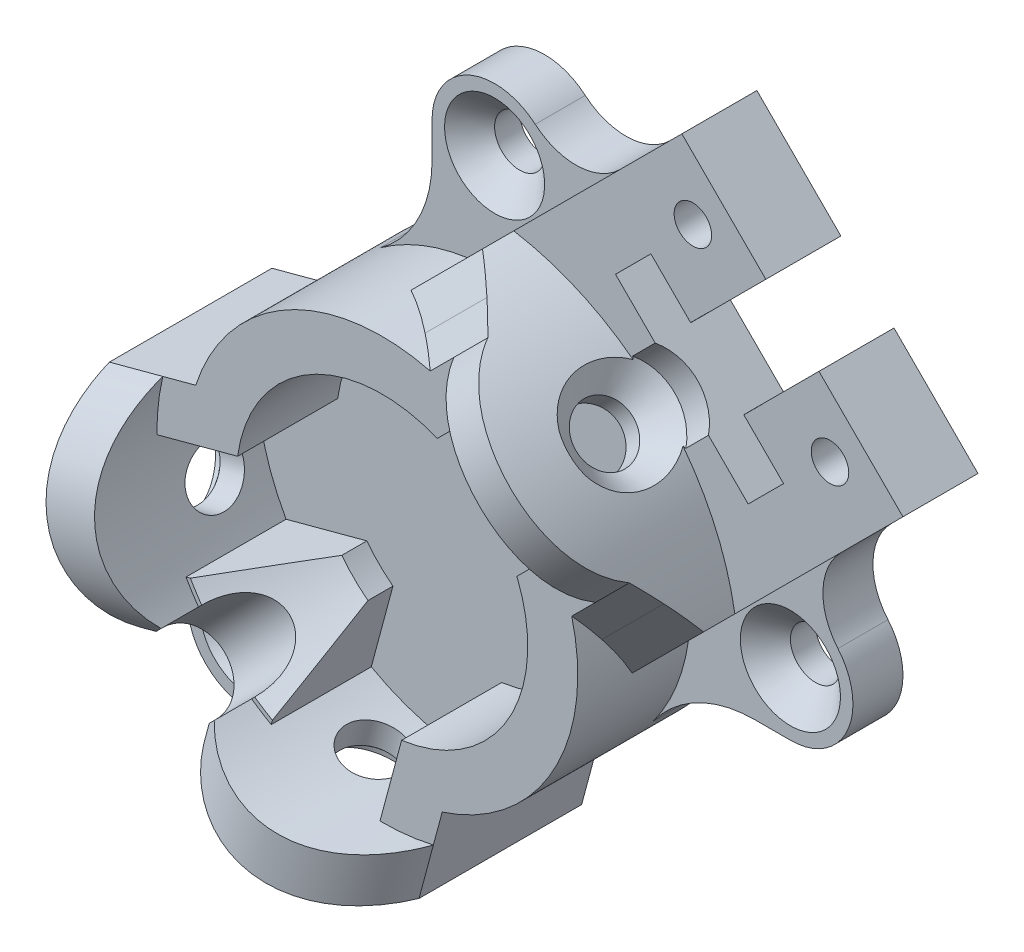
SolidWorks part; units mm, degrees
ref_plane "Top Plane" through (0, 0, 0) normal (0, 0, 1) x (1, 0, 0)
ref_plane "Right Plane" through (0, 0, 0) normal (0, 1, 0) x (1, 0, 0)
ref_plane "Front Plane" through (0, 0, 0) normal (1, 0, 0) x (0, 0, -1)
sketch "Sketch1" plane through (0, 0, 0) normal (0, 0, 1) x (1, 0, 0)
  line L0 (0, 0) -> (-12.3744, -12.3744) construction
  line L4 (-4.5293, -16.9037) -> (0, 0) construction
  line L5 (0, 0) -> (-16.9037, -4.5293) construction
  line L6 (-12.3744, -12.3744) -> (-17.5, -17.5) construction
  line L7 (17.5, -17.5) -> (-17.5, -17.5) construction
  line L8 (-6.5574, -9.0179) -> (-8.2731, -15.4209)
  line L9 (-0.5457, -17.4915) -> (1.17, -11.0884)
  line L10 (-11.0884, 1.17) -> (-17.4915, -0.5457)
  line L11 (-15.4209, -8.2731) -> (-9.0179, -6.5574)
  line L12 (17.5, -17.5) -> (17.5, 17.5)
  line L13 (17.5, 17.5) -> (-17.5, 17.5)
  line L14 (-17.5, -17.5) -> (-17.5, 17.5) construction
  line L15 (17.5, -17.5) -> (-17.5, 17.5) construction
  line L16 (-17.4915, -0.5457) -> (-17.5, -0.548)
  line L17 (-15.4209, -8.2731) -> (-17.5, -8.8302)
  line L18 (-8.2731, -15.4209) -> (-8.8302, -17.5)
  line L19 (-0.5457, -17.4915) -> (-0.548, -17.5)
  line L20 (-17.5, 17.5) -> (-17.5, -0.548)
  line L21 (-17.5, -8.8302) -> (-17.5, -17.5)
  line L22 (-17.5, -17.5) -> (-8.8302, -17.5)
  line L23 (-0.548, -17.5) -> (17.5, -17.5)
  line L24 (10.1879, 4.531) -> (14.8752, 9.2184)
  line L25 (0, 0) -> (12.3744, 12.3744) construction
  line L26 (4.531, 10.1879) -> (9.2184, 14.8752)
  circle A0 centre (0, 0) radius 11.15 construction
  circle A1 centre (0, 0) radius 17.5 construction
  arc A2 (14.8752, 9.2184) -> (9.2184, 14.8752) centre (0, 0) ccw
  arc A8 (-9.0179, -6.5574) -> (-6.5574, -9.0179) centre (0, 0) ccw
  arc A9 (-8.2731, -15.4209) -> (-0.5457, -17.4915) centre (0, 0) ccw construction
  arc A10 (1.17, -11.0884) -> (-11.0884, 1.17) centre (0, 0) ccw
  arc A11 (-17.4915, -0.5457) -> (-15.4209, -8.2731) centre (0, 0) ccw construction
  point P31 (12.3744, 12.3744)
  dimension "D1" = 22.3
  dimension "D2" = 35
  dimension "D3" = 35
  dimension "D4" = 8
  dimension "D5" = 8
  dimension "D6" = 8
  dimension "D7" = 30
  dimension "D8" = 30
sketch "Sketch2" plane through (0, 0, 0) normal (0, 0, 1) x (1, 0, 0)
  line L0 (-0.5457, -17.4915) -> (1.17, -11.0884) construction
  line L5 (-6.5574, -9.0179) -> (-8.2731, -15.4209) construction
  line L6 (-11.0884, 1.17) -> (-17.4915, -0.5457) construction
  line L7 (-15.4209, -8.2731) -> (-9.0179, -6.5574) construction
  line L8 (-0.5457, -17.4915) -> (1.17, -11.0884) construction
  line L9 (-6.5574, -9.0179) -> (-8.2731, -15.4209) construction
  line L10 (-11.0884, 1.17) -> (-17.4915, -0.5457) construction
  line L11 (-15.4209, -8.2731) -> (-9.0179, -6.5574) construction
  line L12 (0.2197, -18.4987) -> (1.9636, -11.9903)
  line L13 (-11.9903, 1.9636) -> (-18.4987, 0.2197)
  line L14 (-15.9105, -9.4396) -> (-9.4021, -7.6957)
  line L15 (-7.6957, -9.4021) -> (-9.4396, -15.9105)
  line L16 (11.3657, 4.2946) -> (16.1302, 9.0591)
  line L17 (12.3744, 12.3744) -> (13.0815, 13.0815) construction
  line L18 (9.0591, 16.1302) -> (4.2946, 11.3657)
  line L19 (0, 0) -> (12.3744, 12.3744) construction
  line L20 (10.1879, 4.531) -> (14.8752, 9.2184) construction
  line L21 (4.531, 10.1879) -> (9.2184, 14.8752) construction
  arc A0 (-9.0179, -6.5574) -> (-6.5574, -9.0179) centre (0, 0) ccw construction
  arc A1 (1.17, -11.0884) -> (-11.0884, 1.17) centre (0, 0) ccw construction
  arc A2 (-9.0179, -6.5574) -> (-6.5574, -9.0179) centre (0, 0) ccw construction
  arc A3 (1.17, -11.0884) -> (-11.0884, 1.17) centre (0, 0) ccw construction
  arc A4 (-17.4915, -0.5457) -> (-15.4209, -8.2731) centre (0, 0) ccw construction
  arc A5 (-8.2731, -15.4209) -> (-0.5457, -17.4915) centre (0, 0) ccw construction
  arc A6 (-9.4396, -15.9105) -> (0.2197, -18.4987) centre (0, 0) ccw
  arc A7 (1.9636, -11.9903) -> (11.3657, 4.2946) centre (0, 0) ccw
  arc A8 (-18.4987, 0.2197) -> (-15.9105, -9.4396) centre (0, 0) ccw
  arc A9 (-9.4021, -7.6957) -> (-7.6957, -9.4021) centre (0, 0) ccw
  arc A10 (16.1302, 9.0591) -> (9.0591, 16.1302) centre (0, 0) ccw
  arc A11 (4.2946, 11.3657) -> (-11.9903, 1.9636) centre (0, 0) ccw
  arc A12 (14.8752, 9.2184) -> (9.2184, 14.8752) centre (0, 0) ccw construction
  arc A14 (11.3657, 4.2946) -> (4.2946, 11.3657) centre (0, 0) ccw construction
  arc A15 (1.9636, -11.9903) -> (-11.9903, 1.9636) centre (0, 0) ccw construction
  point P34 (13.0815, 13.0815)
  dimension "D2" = 1
  dimension "D3" = 1
  dimension "D1" = 1
extrude "Boss-Extrude1" add sketch "Sketch2" against normal blind 5
sketch "Sketch4" plane through (0, 0, 0) normal (0, 0, 1) x (1, 0, 0)
  line L0 (-0.5457, -17.4915) -> (1.17, -11.0884) construction
  line L1 (-6.5574, -9.0179) -> (-8.2731, -15.4209) construction
  line L2 (-15.4209, -8.2731) -> (-9.0179, -6.5574) construction
  line L3 (-11.0884, 1.17) -> (-17.4915, -0.5457) construction
  line L4 (-0.5457, -17.4915) -> (1.17, -11.0884) construction
  line L5 (-6.5574, -9.0179) -> (-8.2731, -15.4209) construction
  line L6 (-15.4209, -8.2731) -> (-9.0179, -6.5574) construction
  line L7 (-11.0884, 1.17) -> (-17.4915, -0.5457) construction
  line L8 (-0.1641, -17.9993) -> (1.5654, -11.5443)
  line L9 (-11.5443, 1.5654) -> (-17.9993, -0.1641)
  line L10 (-15.6699, -8.8575) -> (-9.215, -7.1279)
  line L11 (-7.1279, -9.215) -> (-8.8575, -15.6699)
  line L21 (2.9585, -21.8002) -> (4.8094, -14.8927)
  line L22 (-14.8927, 4.8094) -> (-21.8002, 2.9585)
  line L23 (-17.4002, -13.4622) -> (-12.0208, -12.0208) construction
  line L24 (-12.0208, -12.0208) -> (-13.4622, -17.4002) construction
  line L26 (19.768, 8.4543) -> (13.0163, 1.7026)
  line L27 (1.7026, 13.0163) -> (8.4543, 19.768)
  line L28 (19.768, 8.4543) -> (15.168, 3.8543)
  line L29 (3.8543, 15.168) -> (8.4543, 19.768)
  line L30 (15.168, 3.8543) -> (11.6453, 0.3316) construction
  line L31 (0.3316, 11.6453) -> (3.8543, 15.168) construction
  line L32 (9.1418, 15.5057) -> (4.1775, 10.5414)
  line L33 (10.5414, 4.1775) -> (15.5057, 9.1418)
  line L34 (9.1418, 15.5057) -> (4.4165, 10.7804)
  line L35 (10.7804, 4.4165) -> (15.5057, 9.1418)
  arc A0 (-9.0179, -6.5574) -> (-6.5574, -9.0179) centre (0, 0) ccw construction
  arc A1 (1.17, -11.0884) -> (-11.0884, 1.17) centre (0, 0) ccw construction
  arc A2 (-9.0179, -6.5574) -> (-6.5574, -9.0179) centre (0, 0) ccw construction
  arc A3 (1.17, -11.0884) -> (-11.0884, 1.17) centre (0, 0) ccw construction
  arc A4 (-15.4209, -8.2731) -> (-17.4915, -0.5457) centre (0, 0) cw construction
  arc A5 (-8.2731, -15.4209) -> (-0.5457, -17.4915) centre (0, 0) ccw construction
  arc A6 (-8.8575, -15.6699) -> (-0.1641, -17.9993) centre (0, 0) ccw
  arc A7 (1.5654, -11.5443) -> (11.6453, 0.3316) centre (0, 0) ccw
  arc A8 (-15.6699, -8.8575) -> (-17.9993, -0.1641) centre (0, 0) cw
  arc A9 (-9.215, -7.1279) -> (-7.1279, -9.215) centre (0, 0) ccw
  arc A10 (-13.4622, -17.4002) -> (2.9585, -21.8002) centre (0, 0) ccw
  arc A11 (4.8094, -14.8927) -> (15.168, 3.8543) centre (0, 0) ccw
  arc A12 (-17.4002, -13.4622) -> (-21.8002, 2.9585) centre (0, 0) cw
  arc A13 (-12.0208, -12.0208) -> (-12.0208, -12.0208) centre (-12.0208, -12.0208) cw
  arc A14 (-17.4002, -13.4622) -> (-13.4622, -17.4002) centre (0, 0) ccw
  arc A17 (3.8543, 15.168) -> (-14.8927, 4.8094) centre (0, 0) ccw
  arc A18 (19.768, 8.4543) -> (8.4543, 19.768) centre (0, 0) ccw
  arc A19 (19.768, 8.4543) -> (8.4543, 19.768) centre (0, 0) ccw
  arc A20 (0.3316, 11.6453) -> (-11.5443, 1.5654) centre (0, 0) ccw
  arc A21 (15.168, 3.8543) -> (3.8543, 15.168) centre (0, 0) ccw construction
  arc A22 (4.8094, -14.8927) -> (-14.8927, 4.8094) centre (0, 0) ccw construction
  arc A24 (10.7804, 4.4165) -> (4.4165, 10.7804) centre (0, 0) ccw construction
  arc A25 (1.5654, -11.5443) -> (-11.5443, 1.5654) centre (0, 0) ccw construction
  arc A26 (11.6453, 0.3316) -> (10.7804, 4.4165) centre (0, 0) ccw
  arc A27 (15.5057, 9.1418) -> (9.1418, 15.5057) centre (0, 0) ccw
  arc A28 (15.5057, 9.1418) -> (9.1418, 15.5057) centre (0, 0) ccw
  arc A29 (4.4165, 10.7804) -> (0.3316, 11.6453) centre (0, 0) ccw
  point P30 (15.3806, 8.9996)
  arc M36 (-9.4396, -15.9105) -> (0.2197, -18.4987) centre (0, 0) ccw
  line M37 (0.2197, -18.4987) -> (1.9636, -11.9903)
  arc M38 (1.9636, -11.9903) -> (11.3657, 4.2946) centre (0, 0) ccw
  line M39 (-11.9903, 1.9636) -> (-18.4987, 0.2197)
  arc M40 (-18.4987, 0.2197) -> (-15.9105, -9.4396) centre (0, 0) ccw
  line M41 (-15.9105, -9.4396) -> (-9.4021, -7.6957)
  arc M42 (-9.4021, -7.6957) -> (-7.6957, -9.4021) centre (0, 0) ccw
  line M43 (-7.6957, -9.4021) -> (-9.4396, -15.9105)
  dimension "D2" = 4
  dimension "D1" = 0.5
  dimension "D3" = 4
  dimension "D4" = 0.5
extrude "Boss-Extrude2" add sketch "Sketch4" along normal blind 8 and the other way up to surface (5 mm away) contours A12 A14 A10 L21 A11 L22 M36 M43 M42 M41 M40 M39 M38 M37 | A9 L10 A8 L9 A7 L8 A6 L11 M43 M36 M37 M38 M39 M40 M41 M42 region at (-5.5411, -20.6798, 0) other way up to face at (-2.3894, -2.3894, -5)
sketch "Sketch6" plane through (0, 0, -5) normal (0, 0, -1) x (-1, 0, 0)
  line L0 (-14.8298, -5) -> (-23.65, -5)
  line L1 (-23.65, 5) -> (-14.8298, 5)
  line L2 (0, 0) -> (0, 23.65) construction
  line L3 (-5, 14.8298) -> (-5, 23.65)
  line L4 (5, 23.65) -> (5, 14.8298)
  line L5 (0, 23.65) -> (-23.65, 0) construction
  line L6 (-23.65, 0) -> (0, 0) construction
  line L7 (0, 0) -> (19.5515, -19.5515) construction
  line L8 (6.9507, -14.0218) -> (16.016, -23.087)
  line L9 (23.087, -16.016) -> (14.0218, -6.9507)
  line L10 (0, 0) -> (-11.825, 11.825) construction
  circle A0 centre (0, 23.65) radius 2
  circle A1 centre (-23.65, 0) radius 2
  arc A2 (-15.168, 3.8543) -> (-4.8094, -14.8927) centre (0, 0) ccw construction
  arc A3 (-23.65, -5) -> (-23.65, 5) centre (-23.65, 0) cw
  arc A4 (-5, 23.65) -> (5, 23.65) centre (0, 23.65) cw
  arc A5 (-14.8298, -5) -> (6.9507, -14.0218) centre (0, 0) ccw
  arc A6 (-14.8298, 5) -> (-14.8298, -5) centre (0, 0) ccw construction
  arc A7 (-5, 14.8298) -> (-14.8298, 5) centre (0, 0) ccw
  arc A8 (5, 14.8298) -> (-5, 14.8298) centre (0, 0) ccw construction
  circle A9 centre (19.5515, -19.5515) radius 2
  arc A10 (16.016, -23.087) -> (23.087, -16.016) centre (19.5515, -19.5515) ccw
  arc A11 (14.0218, -6.9507) -> (5, 14.8298) centre (0, 0) ccw
  arc A12 (11.0662, -11.0662) -> (14.0218, -6.9507) centre (0, 0) ccw construction
  arc A13 (6.9507, -14.0218) -> (11.0662, -11.0662) centre (0, 0) ccw construction
  point P18 (0, 15.65)
  dimension "D1" = 3
  dimension "D2" = 4
  dimension "D3" = 8
  dimension "D4" = 12
extrude "Boss-Extrude3" add sketch "Sketch6" against normal blind 4
chamfer "Chamfer2" distance 6 angle 45 1 edges at (-8.2378, -8.2378, 8)
sketch "Sketch7" plane through (0, 0, 8) normal (0, 0, 1) x (1, 0, 0)
  line L0 (-19.5515, -19.5515) -> (0, 0) construction
  line L2 (-19.5515, -19.5515) -> (-17.4302, -21.6728)
  line L3 (-19.5515, -19.5515) -> (0, 0)
  line L4 (0, 0) -> (2.1213, -2.1213)
  line L5 (-17.4302, -21.6728) -> (2.1213, -2.1213)
  circle A0 centre (-19.5515, -19.5515) radius 2 construction
  dimension "D1" = 3
revolve "Cut-Revolve1" cut sketch "Sketch7" angle 360 about L0
ref_plane "Plane2" through (0, 0, 0) normal (0.2588, -0.9659, 0) x (-0.9659, -0.2588, 0)
sketch "Sketch9" plane through (0, 0, 0) normal (0.2588, -0.9659, 0) x (-0.9659, -0.2588, 0)
  line L0 (18, 0) -> (18, -8) construction
  line L1 (25, -4) -> (0, -4)
  line L2 (25, -4) -> (25, -1.7)
  line L3 (25, -1.7) -> (0, -1.7)
  line L4 (0, -4) -> (0, -1.7)
  line L5 (17.4284, -8) -> (18, -8) construction
  line L9 (0, -1.7) -> (0, 0) construction
  point P13 (18, -4)
  dimension "D1" = 2.3
  dimension "D2" = 25
revolve "Cut-Revolve2" cut sketch "Sketch9" angle 360 about L1
ref_plane "Plane3" through (0, 0, 0) normal (0.7071, -0.7071, 0) x (0, 0, -1)
mirror "Mirror1" about plane through (0, 0, 0) normal (0.7071, -0.7071, 0) of "Cut-Revolve2"
sketch "Sketch10" plane through (0, 0, 8) normal (0, 0, 1) x (1, 0, 0)
  line L0 (15.4974, -2.1803) -> (34.6482, 16.9706)
  line L1 (34.6482, 16.9706) -> (16.9706, 34.6482)
  line L2 (16.9706, 34.6482) -> (-2.1803, 15.4974)
  line L3 (13.7809, 7.4169) -> (15.5057, 9.1418)
  line L4 (0, 0) -> (15.2028, 15.2028) construction
  line L5 (15.2028, 15.2028) -> (25.8094, 25.8094) construction
  line L6 (10.7804, 4.4165) -> (15.5057, 9.1418) construction
  line L8 (7.4169, 13.7809) -> (9.1418, 15.5057)
  line L9 (9.1418, 15.5057) -> (4.4165, 10.7804) construction
  arc A2 (-2.1803, 15.4974) -> (7.4169, 13.7809) centre (0, 0) cw
  arc A3 (19.768, 8.4543) -> (8.4543, 19.768) centre (0, 0) ccw construction
  arc A4 (4.8094, -14.8927) -> (15.168, 3.8543) centre (0, 0) ccw construction
  arc A5 (9.1418, 15.5057) -> (15.5057, 9.1418) centre (0, 0) cw
  arc A6 (13.7809, 7.4169) -> (15.4974, -2.1803) centre (0, 0) cw
  arc A7 (11.0662, 11.0662) -> (13.7809, 7.4169) centre (0, 0) cw construction
  arc A8 (7.4169, 13.7809) -> (11.0662, 11.0662) centre (0, 0) cw construction
  arc A9 (15.5057, 9.1418) -> (9.1418, 15.5057) centre (0, 0) ccw construction
  dimension "D1" = 15
  dimension "D2" = 25
extrude "Boss-Extrude4" add sketch "Sketch10" against normal up to surface (13 mm away) from offset 2 up to face at (0.5187, 0.5187, -5) offset against normal yes
sketch "Sketch11" plane through (25.8094, 25.8094, 0) normal (0.7071, 0.7071, 0) x (0, 0, -1)
  line L9 (5, -3.0025) -> (5, 3.0025)
  line L10 (5, 12.5) -> (5, -12.5) construction
  line L11 (5, -3.0025) -> (-1, -3.0025)
  line L12 (-1, -3.0025) -> (-1, -12.5)
  line L13 (5, -12.5) -> (-6, -12.5) construction
  line L14 (-1, -12.5) -> (-6, -12.5)
  line L15 (-6, -12.5) -> (-6, 12.5)
  line L16 (-6, 12.5) -> (-1, 12.5)
  line L17 (5, 12.5) -> (-6, 12.5) construction
  line L18 (-1, 12.5) -> (-1, 3.0025)
  line L19 (-1, 3.0025) -> (5, 3.0025)
  point P5 (5, 0)
  point P6 (5, 0)
  dimension "D1" = 6.005
  dimension "D2" = 6
extrude "Cut-Extrude1" cut sketch "Sketch11" against normal up to surface (15.2107 mm away) up to face at (14.657, 14.657, 7)
fillet "Fillet2" radius 5 2 edges at (5, 22.6777, -3) (22.6777, 5, -3)
fillet "Fillet3" radius 10 2 edges at (14.8298, -5, -3) (-5, 14.8298, -3)
chamfer "Chamfer4" distance 2 angle 45 3 edges at (21.65, 0, -1) (-2, 23.65, -1) (-21.5515, -19.5515, -1)
sketch "Sketch12" plane through (0, 0, 1) normal (0, 0, 1) x (1, 0, 0)
  line L0 (22.2739, 11.6673) -> (11.6673, 22.2739)
  line L1 (11.6673, 22.2739) -> (14.4957, 25.1023)
  line L2 (14.4957, 25.1023) -> (25.1023, 14.4957)
  line L3 (25.1023, 14.4957) -> (22.2739, 11.6673)
  line L4 (0, 0) -> (16.9706, 16.9706) construction
  line L5 (23.6863, 27.9325) -> (16.9706, 34.6482) construction
  line L6 (17.8536, 28.8155) -> (28.8155, 17.8536) construction
  line L7 (19.799, 19.799) -> (23.3345, 23.3345) construction
  line L8 (34.6482, 16.9706) -> (27.9325, 23.6863) construction
  line L9 (17.8536, 28.8155) -> (20.3284, 31.2904) construction
  circle A0 centre (17.8536, 28.8155) radius 1.5
  circle A1 centre (28.8155, 17.8536) radius 1.5
  point P12 (16.8862, 6.3537)
  point P13 (17.3014, 18.2373)
  point P14 (0, 0)
  point P15 (25.5798, 16.2535)
  point P20 (20.8263, 30.7925)
  point P23 (22.6419, 12.0353)
  dimension "D3" = 3
  dimension "D4" = 3.5
  dimension "D1" = 4
  dimension "D2" = 15
  dimension "D5" = 5
extrude "Cut-Extrude2" cut sketch "Sketch12" against normal through all
sketch "Sketch13" plane through (0, 0, 1) normal (0, 0, 1) x (1, 0, 0)
  line L0 (19.0936, 14.8475) -> (14.8475, 19.0936)
  line L4 (14.8475, 19.0936) -> (12.9307, 17.1769)
  line L5 (12.9307, 17.1769) -> (17.1769, 12.9307)
  line L6 (17.1769, 12.9307) -> (19.0936, 14.8475)
extrude "Boss-Extrude5" add sketch "Sketch13" against normal up to surface (6 mm away) up to face at (19.3536, 28.8155, -5)
sketch "Sketch16" plane through (0, 0, 8) normal (0, 0, 1) x (1, 0, 0)
  line L0 (-14.8927, 4.8094) -> (-21.8002, 2.9585) construction
  line L1 (2.9585, -21.8002) -> (4.8094, -14.8927) construction
  line L2 (3.8543, 15.168) -> (8.4543, 19.768) construction
  line L4 (-13.2897, -17.5324) -> (-10.1775, -14.4202) construction
  line L5 (-14.4202, -10.1775) -> (-17.5324, -13.2897) construction
  line L6 (19.768, 8.4543) -> (15.168, 3.8543) construction
  line L7 (-17.5324, -13.2897) -> (-14.6712, -10.4286)
  line L8 (2.9585, -21.8002) -> (4.1038, -17.526)
  line L9 (-13.2897, -17.5324) -> (-10.4286, -14.6712)
  line L10 (17.0586, 5.7449) -> (19.768, 8.4543)
  line L11 (-21.8002, 2.9585) -> (-17.526, 4.1038)
  line L12 (5.7449, 17.0586) -> (8.4543, 19.768)
  arc A0 (19.768, 8.4543) -> (8.4543, 19.768) centre (0, 0) ccw construction
  arc A1 (-13.2897, -17.5324) -> (2.9585, -21.8002) centre (0, 0) ccw construction
  arc A2 (-21.8002, 2.9585) -> (-17.5324, -13.2897) centre (0, 0) ccw construction
  arc A3 (19.768, 8.4543) -> (8.4543, 19.768) centre (0, 0) ccw
  arc A4 (-13.2897, -17.5324) -> (2.9585, -21.8002) centre (0, 0) ccw
  arc A5 (-21.8002, 2.9585) -> (-17.5324, -13.2897) centre (0, 0) ccw
  arc A6 (-17.526, 4.1038) -> (-14.6712, -10.4286) centre (0, 0) ccw
  arc A7 (-10.4286, -14.6712) -> (4.1038, -17.526) centre (0, 0) ccw
  arc A8 (5.7449, 17.0586) -> (17.0586, 5.7449) centre (0, 0) cw
  arc A9 (-8.8575, -15.6699) -> (-0.1641, -17.9993) centre (0, 0) ccw construction
  arc A10 (-17.9993, -0.1641) -> (-15.6699, -8.8575) centre (0, 0) ccw construction
  arc A11 (15.5057, 9.1418) -> (9.1418, 15.5057) centre (0, 0) ccw construction
extrude "Boss-Extrude9" add sketch "Sketch16" along normal blind 10
sketch "Sketch14" plane through (0, 0, 0) normal (0.7071, -0.7071, 0) x (0, 0, -1)
  line L0 (-4, -16.6107) -> (-4, 0) construction
  line L1 (-6.3, 0) -> (-4, 0)
  line L2 (-6.3, 0) -> (-6.3, 19.5)
  line L3 (-6.3, 30) -> (-4, 30)
  line L4 (-4, 0) -> (-4, 30)
  line L5 (-6.3, -15.5885) -> (-6.3, 0) construction
  line L9 (-6.3, 19.5) -> (-8.25, 21.45)
  line L10 (-8.25, 21.45) -> (-8.25, 30)
  line L11 (-8.25, 30) -> (-6.3, 30)
  line L12 (-6.3, 19.5) -> (-6.3, 30) construction
  spline S0 degree 3 poles (-4.3042, -16.6107) (-3.8479, -16.6107) (-3.6983, -16.6049) (-3.4042, -16.582) (-3.258, -16.5647) (-2.9796, -16.5188) (-2.8475, -16.4905) (-2.5976, -16.4225) (-2.4794, -16.3825) (-2.1616, -16.2485) (-1.9903, -16.137) (-1.7607, -15.8838) (-1.7002, -15.7392) (-1.6999, -15.514) (-1.7149, -15.4361) (-1.7736, -15.2822) (-1.8171, -15.2058) (-1.9324, -15.0546) (-2.0043, -14.9803) (-2.1707, -14.8404) (-2.2658, -14.774) (-2.4803, -14.6498) (-2.5963, -14.594) (-2.8452, -14.4953) (-2.9797, -14.452) (-3.2581, -14.3824) (-3.4014, -14.3559) (-3.6964, -14.32) (-3.849, -14.3107) (-4.2995, -14.3106) (-4.6024, -14.3477) (-5.0177, -14.4513) (-5.1516, -14.4941) (-5.4029, -14.5935) (-5.5187, -14.6493) (-5.7309, -14.7719) (-5.8281, -14.8394) (-5.9951, -14.9796) (-6.0658, -15.0526) (-6.1816, -15.2037) (-6.226, -15.2815) (-6.2848, -15.4349) (-6.2999, -15.5114) (-6.3001, -15.6635) (-6.2853, -15.7366) (-6.2271, -15.8774) (-6.1829, -15.9458) (-6.0677, -16.0732) (-5.9971, -16.1323) (-5.8304, -16.242) (-5.7335, -16.2926) (-5.4159, -16.4267) (-5.1596, -16.4958) (-4.6065, -16.5871) (-4.3042, -16.6107) (-3.8479, -16.6107) (-3.6983, -16.6049) knots -0.0625 -0.0625 0 0 0.03125 0.03125 0.0625 0.0625 0.09375 0.09375 0.125 0.125 0.1875 0.1875 0.25 0.25 0.28125 0.28125 0.3125 0.3125 0.34375 0.34375 0.375 0.375 0.40625 0.40625 0.4375 0.4375 0.46875 0.46875 0.5 0.5 0.5625 0.5625 0.59375 0.59375 0.625 0.625 0.65625 0.65625 0.6875 0.6875 0.71875 0.71875 0.75 0.75 0.78125 0.78125 0.8125 0.8125 0.84375 0.84375 0.875 0.875 0.9375 0.9375 1 1 1.03125 1.03125 1.0625 only from (-4, -16.6107) to (-4, -16.6107) construction
  spline S1 degree 3 poles (-4.3042, -16.6107) (-3.8479, -16.6107) (-3.6983, -16.6049) (-3.4042, -16.582) (-3.258, -16.5647) (-2.9796, -16.5188) (-2.8475, -16.4905) (-2.5976, -16.4225) (-2.4794, -16.3825) (-2.1616, -16.2485) (-1.9903, -16.137) (-1.7607, -15.8838) (-1.7002, -15.7392) (-1.6999, -15.514) (-1.7149, -15.4361) (-1.7736, -15.2822) (-1.8171, -15.2058) (-1.9324, -15.0546) (-2.0043, -14.9803) (-2.1707, -14.8404) (-2.2658, -14.774) (-2.4803, -14.6498) (-2.5963, -14.594) (-2.8452, -14.4953) (-2.9797, -14.452) (-3.2581, -14.3824) (-3.4014, -14.3559) (-3.6964, -14.32) (-3.849, -14.3107) (-4.2995, -14.3106) (-4.6024, -14.3477) (-5.0177, -14.4513) (-5.1516, -14.4941) (-5.4029, -14.5935) (-5.5187, -14.6493) (-5.7309, -14.7719) (-5.8281, -14.8394) (-5.9951, -14.9796) (-6.0658, -15.0526) (-6.1816, -15.2037) (-6.226, -15.2815) (-6.2848, -15.4349) (-6.2999, -15.5114) (-6.3001, -15.6635) (-6.2853, -15.7366) (-6.2271, -15.8774) (-6.1829, -15.9458) (-6.0677, -16.0732) (-5.9971, -16.1323) (-5.8304, -16.242) (-5.7335, -16.2926) (-5.4159, -16.4267) (-5.1596, -16.4958) (-4.6065, -16.5871) (-4.3042, -16.6107) (-3.8479, -16.6107) (-3.6983, -16.6049) knots -0.0625 -0.0625 0 0 0.03125 0.03125 0.0625 0.0625 0.09375 0.09375 0.125 0.125 0.1875 0.1875 0.25 0.25 0.28125 0.28125 0.3125 0.3125 0.34375 0.34375 0.375 0.375 0.40625 0.40625 0.4375 0.4375 0.46875 0.46875 0.5 0.5 0.5625 0.5625 0.59375 0.59375 0.625 0.625 0.65625 0.65625 0.6875 0.6875 0.71875 0.71875 0.75 0.75 0.78125 0.78125 0.8125 0.8125 0.84375 0.84375 0.875 0.875 0.9375 0.9375 1 1 1.03125 1.03125 1.0625 only from (-4, -16.6107) to (-4, -16.6107) construction
  dimension "D1" = 30
  dimension "D2" = 45
  dimension "D3" = 2
  dimension "D4" = 4.25
revolve "Cut-Revolve5" cut sketch "Sketch14" angle 360 about L4
sketch "Sketch17" plane through (25.8094, 25.8094, 0) normal (0.7071, 0.7071, 0) x (0, 0, -1)
  line L0 (-8, -8) -> (-8, -10)
  line L1 (-8, -10) -> (-18, -10)
  line L2 (-18, -10) -> (-18, 10)
  line L3 (-18, 10) -> (-8, 10)
  line L4 (-8, 10) -> (-8, 8)
  arc A0 (-8, -8) -> (-8, 8) centre (-4, 0) cw
  circle A2 centre (-4, 0) radius 2.3 construction
  dimension "D1" = 20
  dimension "D2" = 10
extrude "Cut-Extrude3" cut sketch "Sketch17" against normal blind 30
chamfer "Chamfer5" distance 2 angle 45 2 edges at (6.1543, 17.468, 6) (17.468, 6.1543, 6)
ref_axis "Axis1" through (0, 0, -5) along (0, 0, 1)
ref_plane "Plane4" through (-21.2504, -5.694, 0) normal (-0.9659, -0.2588, 0) x (0, 0, 1)
sketch "Sketch18" plane through (-21.2504, -5.694, 0) normal (-0.9659, -0.2588, 0) x (0, 0, 1)
  line L0 (8, -6.0985) -> (8, -6.276) construction
  line L1 (8, 8.5) -> (8, 10)
  line L2 (8, 10) -> (18, 10)
  line L3 (18, 10) -> (18, -10)
  line L4 (18, -10) -> (8, -10)
  line L5 (8, -10) -> (8, -8.5)
  arc A0 (8, 8.5) -> (8, -8.5) centre (4, 0) cw
  circle A2 centre (4, 0) radius 2.3 construction
  dimension "D1" = 20
  dimension "D2" = 10
extrude "Cut-Extrude4" cut sketch "Sketch18" against normal blind 30
sketch "Sketch19" plane through (0, 0, 0) normal (0.2588, -0.9659, 0) x (-0.9659, -0.2588, 0)
  line L0 (0, -4) -> (26.5, -4)
  line L1 (26.5, -4) -> (26.5, -7.7955)
  line L2 (26.5, -7.7955) -> (21.5, -7.7955)
  line L3 (19.5, -5.7955) -> (22, -5.7955) construction
  line L4 (21.5, -7.7955) -> (19.5, -5.7955)
  line L5 (19.5, -5.7955) -> (0, -5.7955)
  line L6 (0, -5.7955) -> (0, -4)
  line L7 (21.9999, -1.7) -> (22, -6.3) construction
  point P7 (22, -4)
  point P9 (21.4516, -7.7955)
  dimension "D1" = 45
  dimension "D2" = 2
  dimension "D3" = 1.7955
  dimension "D4" = 0.5
  dimension "D5" = 5
revolve "Cut-Revolve6" cut sketch "Sketch19" angle 360 about L0
pattern_circular "CirPattern2" count 2 over 60 about axis through (0, 0, -5) along (0, 0, 1) of "Cut-Extrude4", "Cut-Revolve6"
chamfer "Chamfer6" distance 2.5 angle 45 2 edges at (18.3528, 0.6751, 6) (0.6751, 18.3528, 6)
